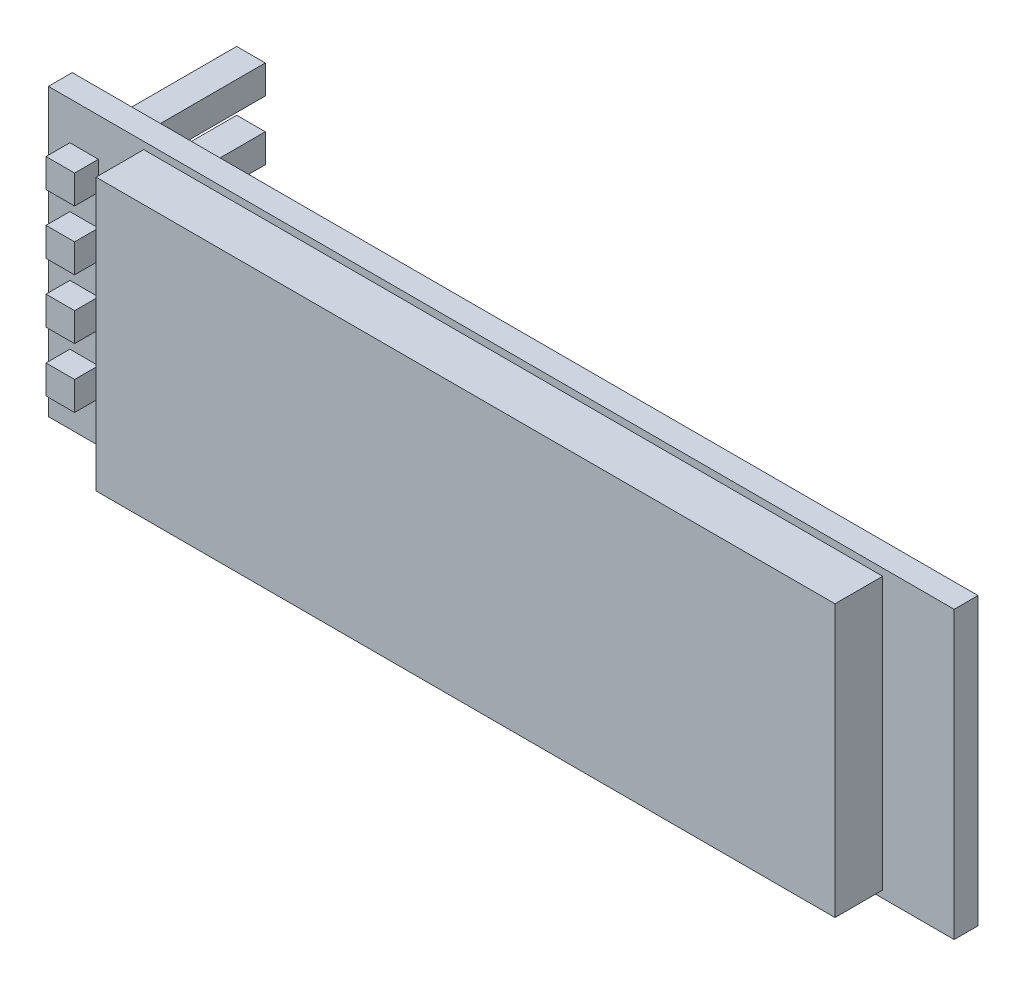
SolidWorks part; units mm, degrees
ref_plane "正面" through (0, 0, 0) normal (0, 0, 1) x (1, 0, 0)
ref_plane "平面" through (0, 0, 0) normal (0, 1, 0) x (1, 0, 0)
ref_plane "右側面" through (0, 0, 0) normal (1, 0, 0) x (0, 0, -1)
sketch "ｽｹｯﾁ1" plane through (0, 0, 0) normal (0, 0, 1) x (1, 0, 0)
  line L1 (-19, -6) -> (19, -6)
  line L2 (-19, -6) -> (-19, 6)
  line L3 (-19, 6) -> (19, 6)
  line L4 (19, -6) -> (19, 6)
  line L5 (-19, -6) -> (19, 6) construction
  line L6 (-19, 6) -> (19, -6) construction
  point P0 (0, 0)
  point P10 (0.5, 0)
  dimension "D1" = 38
  dimension "D2" = 12
sketch "ｽｹｯﾁ2" plane through (0, 0, 0) normal (0, 0, 1) x (1, 0, 0)
  line L0 (-15, 5.7) -> (-15, -5.7)
  line L1 (-19, -6) -> (19, -6) construction
  line L2 (-19, -6) -> (-19, 6) construction
  line L3 (-19, 6) -> (19, 6) construction
  line L4 (19, -6) -> (19, 6) construction
  line L5 (-19, -6) -> (19, 6) construction
  line L6 (-19, 6) -> (19, -6) construction
  line L7 (16, 5.7) -> (-15, 5.7)
  line L8 (16, 5.7) -> (16, -5.7)
  line L9 (16, -5.7) -> (-15, -5.7)
  line L11 (16, 5.7) -> (-15, -5.7) construction
  line L12 (16, -5.7) -> (-15, 5.7) construction
  point P0 (0, 0)
  point P10 (0.5, 0)
  dimension "D1" = 38
  dimension "D2" = 12
  dimension "D3" = 3
  dimension "D4" = 0.3
  dimension "D5" = 0.3
extrude "ﾎﾞｽ - 押し出し4" add sketch "ｽｹｯﾁ1" along normal blind 1
sketch "ｽｹｯﾁ3" plane through (0, 0, 0) normal (0, 0, 1) x (1, 0, 0)
  line L0 (-17.5, 6) -> (-17.5, -6) construction
  line L1 (-19, -6) -> (19, -6) construction
  line L2 (-19, -6) -> (-19, 6) construction
  line L3 (-19, 6) -> (19, 6) construction
  line L4 (19, -6) -> (19, 6) construction
  line L5 (-19, -6) -> (19, 6) construction
  line L6 (-19, 6) -> (19, -6) construction
  line L14 (-18.1, 3.2) -> (-16.9, 3.2)
  line L15 (-18.1, 3.2) -> (-18.1, 4.4)
  line L16 (-18.1, 4.4) -> (-16.9, 4.4)
  line L17 (-16.9, 3.2) -> (-16.9, 4.4)
  line L18 (-18.1, 3.2) -> (-16.9, 4.4) construction
  line L19 (-18.1, 4.4) -> (-16.9, 3.2) construction
  line L20 (-18.1, 0.7) -> (-16.9, 0.7)
  line L21 (-18.1, 0.7) -> (-18.1, 1.9)
  line L22 (-18.1, 1.9) -> (-16.9, 1.9)
  line L23 (-16.9, 0.7) -> (-16.9, 1.9)
  line L24 (-18.1, 0.7) -> (-16.9, 1.9) construction
  line L25 (-18.1, 1.9) -> (-16.9, 0.7) construction
  line L26 (-18.1, -1.8) -> (-16.9, -1.8)
  line L27 (-18.1, -1.8) -> (-18.1, -0.6)
  line L28 (-18.1, -0.6) -> (-16.9, -0.6)
  line L29 (-16.9, -1.8) -> (-16.9, -0.6)
  line L30 (-18.1, -1.8) -> (-16.9, -0.6) construction
  line L31 (-18.1, -0.6) -> (-16.9, -1.8) construction
  line L32 (-18.1, -4.3) -> (-16.9, -4.3)
  line L33 (-18.1, -4.3) -> (-18.1, -3.1)
  line L34 (-18.1, -3.1) -> (-16.9, -3.1)
  line L35 (-16.9, -4.3) -> (-16.9, -3.1)
  line L36 (-18.1, -4.3) -> (-16.9, -3.1) construction
  line L37 (-18.1, -3.1) -> (-16.9, -4.3) construction
  point P0 (0, 0)
  point P10 (0.5, 0)
  point P13 (-17.5, 3.8)
  point P18 (-17.5, 1.3)
  point P23 (-17.5, -1.2)
  point P28 (-17.5, -3.7)
  dimension "D1" = 38
  dimension "D2" = 12
  dimension "D7" = 1.5
  dimension "D8" = 1.2
  dimension "D9" = 1.2
  dimension "D10" = 1.6
  dimension "D11" = 1.3
  dimension "D12" = 1.3
  dimension "D13" = 1.3
extrude "ﾎﾞｽ - 押し出し5" add sketch "ｽｹｯﾁ2" along normal blind 3
extrude "ﾎﾞｽ - 押し出し6" add sketch "ｽｹｯﾁ3" along normal blind 2
extrude "ﾎﾞｽ - 押し出し7" add sketch "ｽｹｯﾁ3<5>" along normal blind 2 and the other way blind 6
sketch "ｽｹｯﾁ3<5>" plane through (0, 0, 0) normal (0, 0, 1) x (1, 0, 0) same geometry as "ｽｹｯﾁ3"
